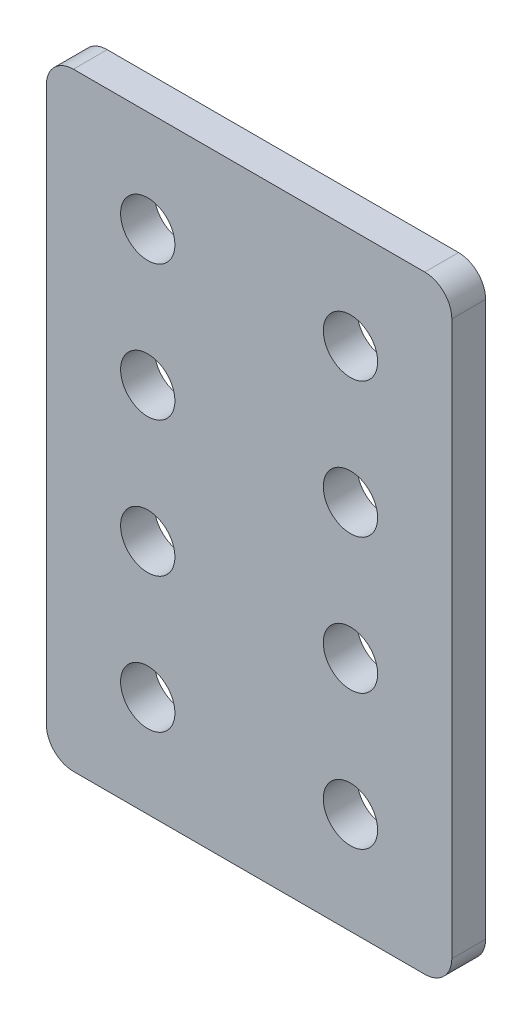
SolidWorks part; units mm, degrees
material "6061-T6 (SS)"
ref_plane "Front Plane" through (0, 0, 0) normal (0, 0, 1) x (1, 0, 0)
ref_plane "Top Plane" through (0, 0, 0) normal (0, 1, 0) x (1, 0, 0)
ref_plane "Right Plane" through (0, 0, 0) normal (1, 0, 0) x (0, 0, -1)
sketch "Sketch1" plane through (0, 0, 0) normal (0, 0, 1) x (1, 0, 0)
  line L0 (-9.525, -19.05) -> (-9.525, -6.35) construction
  line L5 (-19.05, -28.575) -> (19.05, -28.575)
  line L6 (-19.05, -28.575) -> (-19.05, 28.575)
  line L11 (-19.05, 28.575) -> (19.05, 28.575)
  line L15 (19.05, -28.575) -> (19.05, 28.575)
  line L16 (-19.05, -28.575) -> (19.05, 28.575) construction
  line L17 (-19.05, 28.575) -> (19.05, -28.575) construction
  line L18 (0, 28.575) -> (0, -28.575) construction
  circle A13 centre (-9.525, -19.05) radius 2.5527
  circle A14 centre (-9.525, -6.35) radius 2.5527
  circle A15 centre (-9.525, 6.35) radius 2.5527
  circle A16 centre (-9.525, 19.05) radius 2.5527
  circle A17 centre (9.525, -19.05) radius 2.5527
  circle A18 centre (9.525, -6.35) radius 2.5527
  circle A19 centre (9.525, 6.35) radius 2.5527
  circle A20 centre (9.525, 19.05) radius 2.5527
  point P0 (0, 0)
  dimension "D2" = 12.7
  dimension "D4" = 9.525
  dimension "D5" = 19.05
  dimension "D3" = 9.525
  dimension "D7" = 5.1054
  dimension "D1" = 4
  dimension "D6" = 38.1
extrude "Boss-Extrude1" add sketch "Sketch1" along normal blind 3.175
fillet "Fillet1" radius 2.54 4 edges at (-19.05, 28.575, 1.5875) (-19.05, -28.575, 1.5875) (19.05, -28.575, 1.5875) (19.05, 28.575, 1.5875)
